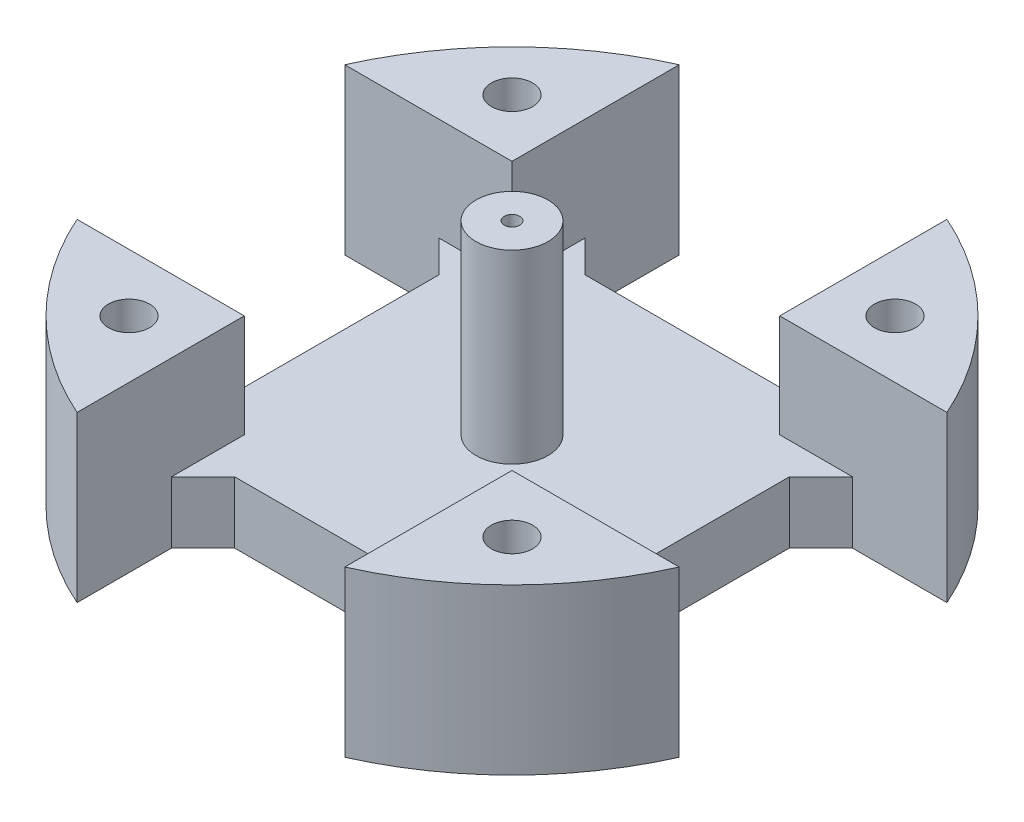
SolidWorks part; units mm, degrees
note: The reader was unsure of these and kept them because the rebuilt part matched: shared geometry of "Croquis6<6>", "Croquis10<3>".
ref_plane "Alzado" through (0, 0, 0) normal (0, 0, 1) x (1, 0, 0)
ref_plane "Planta" through (0, 0, 0) normal (0, 1, 0) x (1, 0, 0)
ref_plane "Vista lateral" through (0, 0, 0) normal (1, 0, 0) x (0, 0, -1)
sketch "Croquis1" plane through (0, 0, 0) normal (0, 1, 0) x (1, 0, 0)
  circle A0 centre (0, 0) radius 16
  dimension "D1" = 32
extrude "Saliente-Extruir1" add sketch "Croquis1" along normal blind 8
sketch "Croquis2" plane through (0, 0, 0) normal (0, -1, 0) x (-1, 0, 0)
  line L0 (0, -16) -> (0, 16) construction
  line L1 (16, 0) -> (-16, 0) construction
  line L2 (8.5, -13.5554) -> (8.5, 13.5554) construction
  line L3 (-8.5, -13.5554) -> (-8.5, 13.5554) construction
  line L4 (13.5554, -8.5) -> (-13.5554, -8.5) construction
  line L5 (13.5554, 8.5) -> (-13.5554, 8.5) construction
  line L6 (0, 0) -> (-11.3137, -11.3137) construction
  line L7 (0, 0) -> (11.3137, 11.3137) construction
  line L8 (-12.9425, -9.407) -> (9.407, 12.9425) construction
  line L9 (-9.407, -12.9425) -> (12.9425, 9.407) construction
  line L10 (11.3137, -11.3137) -> (-11.3137, 11.3137) construction
  line L11 (9.407, -12.9425) -> (-12.9425, 9.407) construction
  line L12 (12.9425, -9.407) -> (-9.407, 12.9425) construction
  line L13 (14.6202, 6.5) -> (-14.6202, 6.5) construction
  line L14 (14.6202, -6.5) -> (-14.6202, -6.5) construction
  line L15 (6.5, -14.6202) -> (6.5, 14.6202) construction
  line L16 (-6.5, -14.6202) -> (-6.5, 14.6202) construction
  line L17 (14.6202, -6.5) -> (10.0355, -6.5)
  line L18 (10.0355, -6.5) -> (8.5, -4.9645)
  line L19 (8.5, -4.9645) -> (8.5, 4.9645)
  line L20 (8.5, 4.9645) -> (10.0355, 6.5)
  line L21 (10.0355, 6.5) -> (14.6202, 6.5)
  line L22 (-10.0355, 6.5) -> (-14.6202, 6.5)
  line L23 (-8.5, 4.9645) -> (-10.0355, 6.5)
  line L24 (-8.5, -4.9645) -> (-8.5, 4.9645)
  line L25 (-10.0355, -6.5) -> (-8.5, -4.9645)
  line L26 (-14.6202, -6.5) -> (-10.0355, -6.5)
  line L27 (6.5, -14.6202) -> (6.5, -10.0355)
  line L28 (6.5, -10.0355) -> (4.9645, -8.5)
  line L29 (4.9645, -8.5) -> (-4.9645, -8.5)
  line L30 (-4.9645, -8.5) -> (-6.5, -10.0355)
  line L31 (-6.5, -10.0355) -> (-6.5, -14.6202)
  line L32 (6.5, 14.6202) -> (6.5, 10.0355)
  line L33 (6.5, 10.0355) -> (4.9645, 8.5)
  line L34 (4.9645, 8.5) -> (-4.9645, 8.5)
  line L35 (-4.9645, 8.5) -> (-6.5, 10.0355)
  line L36 (-6.5, 10.0355) -> (-6.5, 14.6202)
  circle A0 centre (0, 0) radius 16 construction
  arc A1 (14.6202, -6.5) -> (16, 0) centre (0, 0) cw
  arc A2 (6.5, -14.6202) -> (0, -16) centre (0, 0) ccw
  arc A3 (6.5, 14.6202) -> (0, 16) centre (0, 0) cw
  dimension "D1" = 8.5
  dimension "D2" = 8.5
  dimension "D3" = 8.5
  dimension "D4" = 8.5
  dimension "D5" = 2.5
  dimension "D6" = 2.5
  dimension "D7" = 6.5
  dimension "D8" = 6.5
extrude "Cortar-Extruir2" cut sketch "Croquis2" against normal blind 10 contours L30 L31 L0 A1 L27 L28 L29 | L21 L20 L19 L18 L17 L0 | L0 L26 L25 L24 L23 L22 | L36 L35 L34 L33 L32 L0 A2
sketch "Croquis4" plane through (0, 0, 0) normal (0, -1, 0) x (1, 0, 0)
  line L0 (-8.5, 0) -> (8.5, 0) construction
  line L1 (-8.5, 4.9645) -> (-8.5, -4.9645) construction
  line L2 (8.5, 4.9645) -> (8.5, -4.9645) construction
  line L3 (-8.5, 6.5) -> (8.5, 6.5) construction
  line L4 (-19.3208, 0) -> (20.9643, 0) construction
  line L5 (20.9643, 0) -> (20.9643, 6.5) construction
  line L6 (20.9643, 6.5) -> (-19.3208, 6.5) construction
  line L7 (-19.3208, 6.5) -> (-19.3208, -6.5) construction
  line L8 (-19.3208, -6.5) -> (20.9643, -6.5) construction
  line L9 (20.9643, -6.5) -> (20.9643, 0) construction
  line L10 (0, 16.5994) -> (0, -17.2962) construction
  line L11 (0, -17.2962) -> (6.5, -17.2962) construction
  line L12 (6.5, -17.2962) -> (6.5, 16.5994) construction
  line L13 (6.5, 16.5994) -> (-6.5, 16.5994) construction
  line L14 (-6.5, 16.5994) -> (-6.5, -17.2962) construction
  line L15 (-6.5, -17.2962) -> (0, -17.2962) construction
  line L16 (-6.5, 16.5994) -> (-6.5, 6.5)
  line L17 (-6.5, 6.5) -> (-19.3208, 6.5)
  line L18 (-19.3208, 6.5) -> (-19.3208, -6.5)
  line L19 (-19.3208, -6.5) -> (-6.5, -6.5)
  line L20 (-6.5, -6.5) -> (-6.5, -17.2962)
  line L21 (-6.5, -17.2962) -> (6.5, -17.2962)
  line L22 (6.5, -17.2962) -> (6.5, -6.5)
  line L23 (6.5, -6.5) -> (20.9643, -6.5)
  line L24 (20.9643, -6.5) -> (20.9643, 6.5)
  line L25 (20.9643, 6.5) -> (6.5, 6.5)
  line L26 (6.5, 6.5) -> (6.5, 16.5994)
  line L27 (6.5, 16.5994) -> (-6.5, 16.5994)
  dimension "D1" = 6.5
extrude "Cortar-Extruir4" cut sketch "Croquis4" against normal blind 10 and the other way blind 5 from vertex at -8 starting at point (6.5, 8, 14.6202)
sketch "Croquis5" plane through (0, 3, 0) normal (0, 1, 0) x (1, 0, 0)
  circle A0 centre (0, 0) radius 1.75
extrude "Saliente-Extruir2" add sketch "Croquis5" along normal blind 9
sketch "Croquis6" plane through (0, 8, 0) normal (0, 1, 0) x (1, 0, 0)
  line L0 (-11.3137, 11.3137) -> (11.3137, -11.3137) construction
  line L1 (11.3137, 11.3137) -> (-11.3137, -11.3137) construction
  arc A1 (-6.5, 14.6202) -> (-14.6202, 6.5) centre (0, 0) ccw construction
  arc A2 (6.5, -14.6202) -> (14.6202, -6.5) centre (0, 0) ccw construction
  arc A3 (14.6202, 6.5) -> (6.5, 14.6202) centre (0, 0) ccw construction
  arc A4 (-14.6202, -6.5) -> (-6.5, -14.6202) centre (0, 0) ccw construction
  circle A5 centre (-9.2985, 9.2985) radius 2.8
  circle A6 centre (9.2985, -9.2985) radius 2.8
  circle A7 centre (-9.2985, -9.2985) radius 1
  circle A8 centre (-9.2985, -9.2985) radius 2.8
  circle A9 centre (-9.2985, 9.2985) radius 2.8
  circle A10 centre (9.2985, 9.2985) radius 2.8
  circle A11 centre (-9.2985, 9.2985) radius 1
  circle A12 centre (9.2985, 9.2985) radius 1
  circle A13 centre (9.2985, -9.2985) radius 1
  point P34 (0, 0)
  point P41 (0, 0)
  line M1 (6.5, 14.6202) -> (6.5, 6.5)
  line M2 (6.5, 6.5) -> (14.6202, 6.5)
  dimension "D2" = 4
  dimension "D3" = 4
extrude "Saliente-Extruir4" [suppressed] add sketch "Croquis6" along normal blind 2 contours A8 A7 | A5 A11 | A10 A12 M2 M1 | A6 A13
sketch "Croquis9" [suppressed] plane through (0, 8, 0) normal (0, 1, 0) x (1, 0, 0)
  circle A0 centre (-9.2985, 9.2985) radius 1
  circle A1 centre (9.2985, 9.2985) radius 1
  circle A2 centre (9.2985, -9.2985) radius 1
  circle A3 centre (-9.2985, -9.2985) radius 1
  point P12 (0, 0)
  dimension "D1" = 4
extrude "Cortar-Extruir5" [suppressed] cut sketch "Croquis9" against normal blind 12
sketch "Croquis10" plane through (0, 0, 0) normal (0, -1, 0) x (1, 0, 0)
  circle A0 centre (0, 0) radius 6.75
extrude "Saliente-Extruir5" [suppressed] add sketch "Croquis10" along normal blind 2
sketch "Croquis11" [suppressed] plane through (0, -2, 0) normal (0, -1, 0) x (1, 0, 0)
  circle A0 centre (0, 0) radius 6
extrude "Cortar-Extruir6" [suppressed] cut sketch "Croquis11" against normal blind 4
sketch "Croquis12" [suppressed] plane through (0, -2, 0) normal (0, -1, 0) x (1, 0, 0)
  circle A0 centre (0, 0) radius 0.375
extrude "Cortar-Extruir7" [suppressed] cut sketch "Croquis12" against normal blind 7
extrude "Cortar-Extruir8" cut sketch "Croquis6<6>" against normal blind 10 contours A11 | A12 | A13 | A7
sketch "Croquis6<6>" plane through (0, 8, 0) normal (0, 1, 0) x (1, 0, 0) same geometry as "Croquis6"
extrude "Cortar-Extruir10" cut sketch "Croquis10<3>" against normal blind 2
sketch "Croquis10<3>" plane through (0, 0, 0) normal (0, -1, 0) x (1, 0, 0) same geometry as "Croquis10"
sketch "Croquis13" plane through (0, 0, 0) normal (0, -1, 0) x (1, 0, 0)
  circle A0 centre (0, 0) radius 0.375
extrude "Cortar-Extruir11" cut sketch "Croquis13" against normal blind 22
